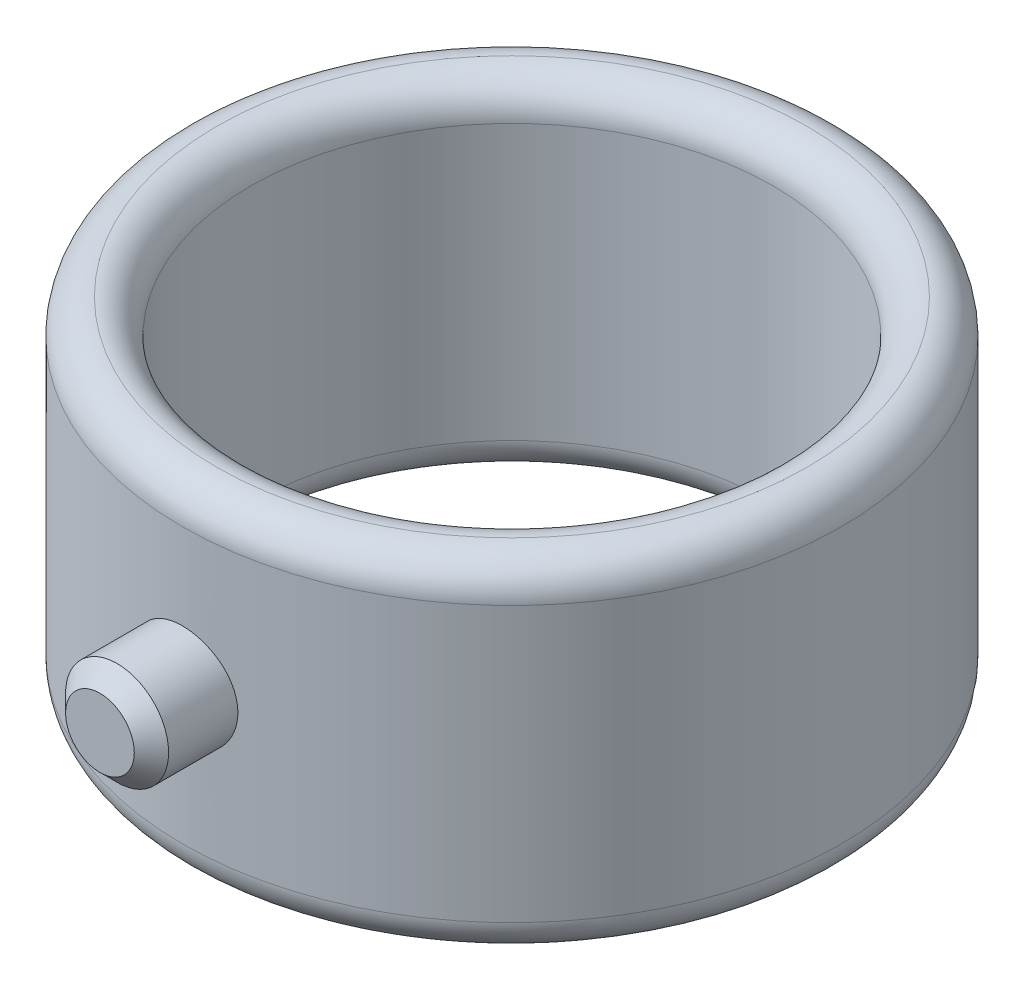
SolidWorks part; units mm, degrees
ref_plane "Front" through (0, 0, 0) normal (0, 0, 1) x (1, 0, 0)
ref_plane "Top" through (0, 0, 0) normal (0, 1, 0) x (1, 0, 0)
ref_plane "Right" through (0, 0, 0) normal (1, 0, 0) x (0, 0, -1)
sketch "Sketch1" plane through (0, 0, 0) normal (0, 1, 0) x (1, 0, 0)
  circle A1 centre (0, 0) radius 9.6
extrude "Boss-Extrude1" add sketch "Sketch1" along normal blind 10
sketch "Sketch2" plane through (0, 0, 0) normal (0, 0, 1) x (1, 0, 0)
  circle A0 centre (0, 5) radius 1.5
  dimension "D1" = 5
extrude "Boss-Extrude2" add sketch "Sketch2" along normal blind 12 and the other way blind 12
sketch "Sketch3" plane through (0, 10, 0) normal (0, 1, 0) x (1, 0, 0)
  circle A0 centre (0, 0) radius 7.6
extrude "Cut-Extrude1" cut sketch "Sketch3" against normal blind 12
fillet "Fillet1" radius 1 4 edges at (0, 0, 7.6) (0, 10, 7.6) (0, 0, 9.6) (0, 10, 9.6)
chamfer "Chamfer1" distance 0.5 angle 45 2 edges at (1.5, 5, -12) (1.5, 5, 12)
